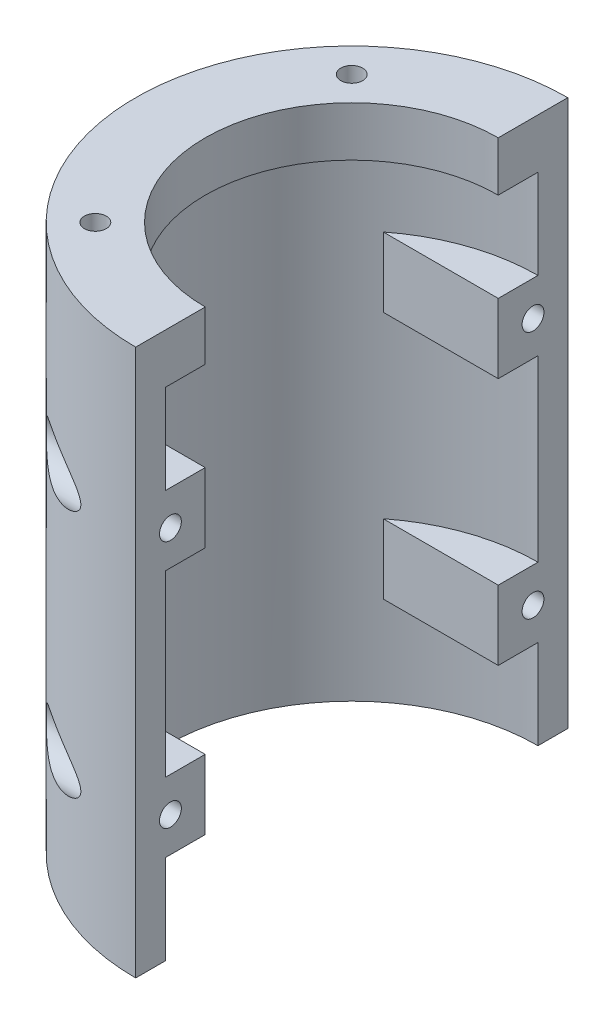
SolidWorks part; units mm, degrees
ref_plane "正面" through (0, 0, 0) normal (0, 0, 1) x (1, 0, 0)
ref_plane "平面" through (0, 0, 0) normal (0, 1, 0) x (1, 0, 0)
ref_plane "右側面" through (0, 0, 0) normal (1, 0, 0) x (0, 0, -1)
sketch "ｽｹｯﾁ1" plane through (0, 0, 0) normal (0, 1, 0) x (1, 0, 0)
  line L0 (0, -21.75) -> (0, -14.75)
  line L1 (0, -14.75) -> (0, 14.75) construction
  line L2 (0, 14.75) -> (0, 21.75)
  arc A0 (0, 21.75) -> (0, -21.75) centre (0, 0) ccw
  arc A1 (0, 14.75) -> (0, -14.75) centre (0, 0) ccw
  dimension "D1" = 14.75
  dimension "D2" = 7
extrude "ﾎﾞｽ - 押し出し1" add sketch "ｽｹｯﾁ1" along normal blind 55
sketch "ｽｹｯﾁ2" plane through (0, 55, 0) normal (0, 1, 0) x (1, 0, 0)
  circle A0 centre (0, 0) radius 14.75
  circle A1 centre (0, 0) radius 18.75
  arc A2 (0, 14.75) -> (0, -14.75) centre (0, 0) ccw construction
  arc A3 (0, 21.75) -> (0, -21.75) centre (0, 0) ccw construction
  dimension "D1" = 3
extrude "ｶｯﾄ - 押し出し1" cut sketch "ｽｹｯﾁ2" against normal through all from offset 5 offset against normal yes
sketch "ｽｹｯﾁ4" plane through (0, 0, 0) normal (1, 0, 0) x (0, 0, -1)
  line L0 (-14.75, 12.5) -> (-21.75, 12.5) construction
  line L1 (-21.75, 41) -> (-21.75, 34)
  line L2 (-18.75, 50) -> (-14.75, 50) construction
  line L3 (21.75, 55) -> (21.75, 0) construction
  line L4 (18.75, 50) -> (18.75, 0) construction
  line L5 (-21.75, 16) -> (-14.75, 16)
  line L6 (-14.75, 16) -> (-14.75, 9)
  line L7 (-14.75, 9) -> (-21.75, 9)
  line L8 (-21.75, 9) -> (-21.75, 16)
  line L9 (-21.75, 50) -> (21.75, 50) construction
  line L10 (0, 25) -> (-21.75, 25) construction
  line L11 (0, 25) -> (21.75, 25) construction
  line L12 (-21.75, 37.5) -> (21.75, 37.5) construction
  line L13 (-21.75, 0) -> (21.75, 0) construction
  line L14 (0, 50) -> (0, 0) construction
  line L15 (-18.25, 50) -> (-18.25, 0) construction
  line L16 (18.75, 50) -> (18.75, 37.5) construction
  line L17 (18.75, 37.5) -> (18.75, 25) construction
  line L18 (-21.75, 55) -> (-21.75, 0) construction
  line L19 (-21.75, 34) -> (-14.75, 34)
  line L20 (-14.75, 34) -> (-14.75, 41)
  line L21 (-14.75, 41) -> (-21.75, 41)
  line L22 (21.75, 9) -> (21.75, 16)
  line L23 (21.75, 16) -> (14.75, 16)
  line L24 (14.75, 16) -> (14.75, 9)
  line L25 (14.75, 9) -> (21.75, 9)
  line L26 (21.75, 34) -> (14.75, 34)
  line L27 (21.75, 41) -> (21.75, 34)
  line L28 (14.75, 41) -> (21.75, 41)
  line L29 (14.75, 34) -> (14.75, 41)
  circle A0 centre (-18.25, 37.5) radius 1.1 construction
  circle A1 centre (18.25, 37.5) radius 1.1 construction
  circle A2 centre (18.25, 12.5) radius 1.1 construction
  circle A3 centre (-18.25, 12.5) radius 1.1 construction
  dimension "D1" = 2.2
  dimension "D2" = 3.5
  dimension "D3" = 7
  dimension "D4" = 7
extrude "ﾎﾞｽ - 押し出し3" add sketch "ｽｹｯﾁ4" against normal up to next
sketch "ｽｹｯﾁ3" plane through (0, 0, 0) normal (1, 0, 0) x (0, 0, -1)
  line L0 (-21.75, 50) -> (21.75, 50) construction
  line L1 (0, 25) -> (-21.75, 25) construction
  line L2 (0, 25) -> (21.75, 25) construction
  line L3 (-21.75, 55) -> (-21.75, 0) construction
  line L4 (-21.75, 37.5) -> (21.75, 37.5) construction
  line L5 (21.75, 55) -> (21.75, 0) construction
  line L6 (-21.75, 0) -> (21.75, 0) construction
  line L7 (0, 50) -> (0, 0) construction
  line L8 (14.75, 50) -> (18.75, 50) construction
  line L9 (-18.25, 50) -> (-18.25, 0) construction
  line L10 (18.75, 50) -> (18.75, 37.5) construction
  line L11 (18.75, 37.5) -> (18.75, 25) construction
  line L12 (18.75, 50) -> (18.75, 41) construction
  circle A0 centre (-18.25, 37.5) radius 1.1
  circle A1 centre (18.25, 37.5) radius 1.1
  circle A2 centre (18.25, 12.5) radius 1.1
  circle A3 centre (-18.25, 12.5) radius 1.1
  dimension "D1" = 2.2
  dimension "D2" = 3.5
extrude "ｶｯﾄ - 押し出し2" cut sketch "ｽｹｯﾁ3" against normal blind 5
sketch "ｽｹｯﾁ5" plane through (0, 0, 0) normal (1, 0, 0) x (0, 0, -1)
  circle A0 centre (-18.25, 37.5) radius 2.5
  circle A1 centre (-18.25, 12.5) radius 2.5
  circle A2 centre (18.25, 12.5) radius 2.5
  circle A3 centre (18.25, 37.5) radius 2.5
  dimension "D1" = 5
extrude "ｶｯﾄ - 押し出し3" cut sketch "ｽｹｯﾁ5" against normal through all from offset 4 offset against normal yes
sketch "ｽｹｯﾁ6" plane through (0, 55, 0) normal (0, 1, 0) x (1, 0, 0)
  line L0 (0, 0) -> (-14.75, 0) construction
  line L1 (-14.75, 0) -> (-18.25, 0) construction
  line L2 (-18.25, 0) -> (-21.75, 0) construction
  line L3 (0, 0) -> (-12.9047, -12.9047) construction
  line L4 (-12.9047, 12.9047) -> (0, 0) construction
  circle A0 centre (0, 0) radius 18.25 construction
  arc A1 (0, 14.75) -> (0, -14.75) centre (0, 0) ccw construction
  arc A2 (0, 21.75) -> (0, -21.75) centre (0, 0) ccw construction
  circle A3 centre (-12.9047, -12.9047) radius 1.1
  circle A4 centre (-12.9047, 12.9047) radius 1.1
  dimension "D2" = 2.2
  dimension "D1" = 45
  dimension "D4" = 90
  dimension "D3" = 2
extrude "ｶｯﾄ - 押し出し4" cut sketch "ｽｹｯﾁ6" against normal up to vertex (5 mm away) up to point (0, 50, -14.75)
